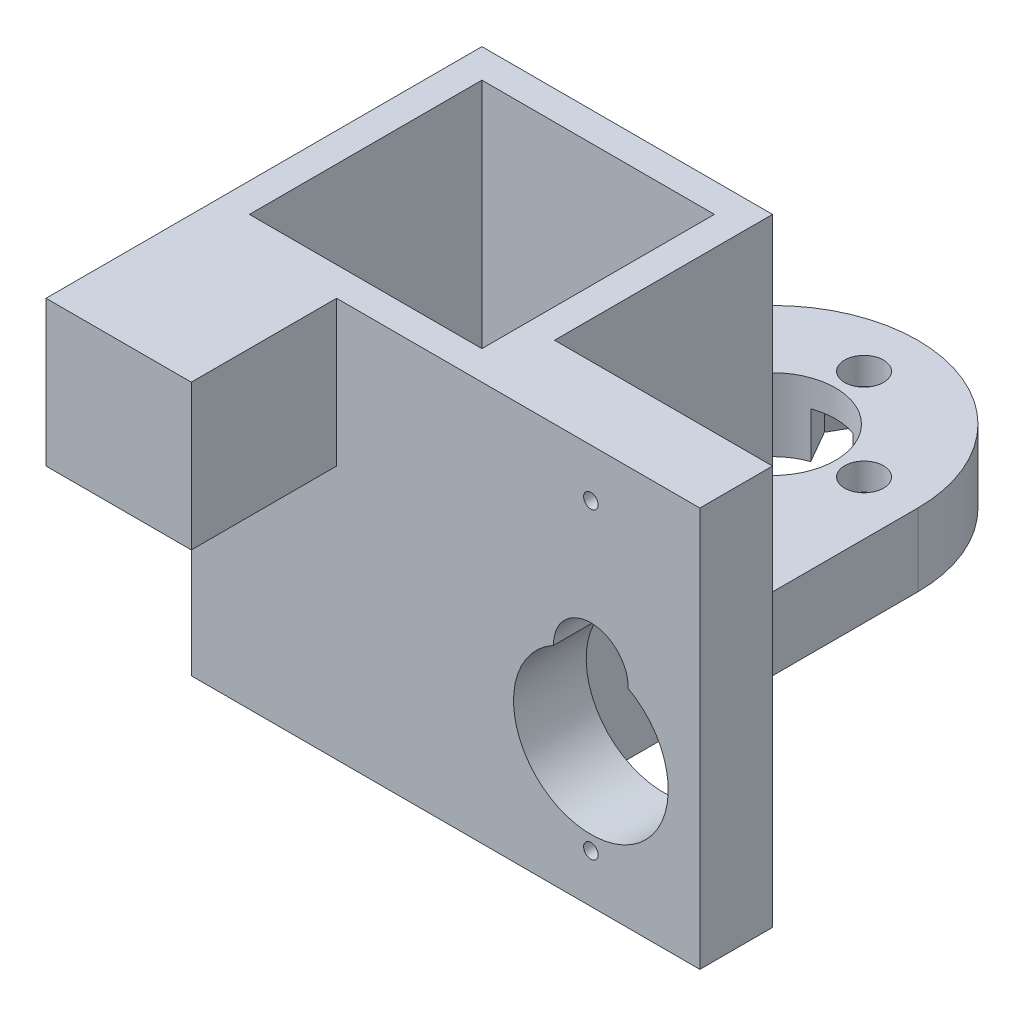
SolidWorks part; units mm, degrees
ref_plane "Front Plane" through (0, 0, 0) normal (0, 0, 1) x (1, 0, 0)
ref_plane "Top Plane" through (0, 0, 0) normal (0, 1, 0) x (1, 0, 0)
ref_plane "Right Plane" through (0, 0, 0) normal (1, 0, 0) x (0, 0, -1)
sketch "Sketch1" plane through (0, 0, 0) normal (0, 1, 0) x (1, 0, 0)
  line L1 (-10.16, 10.16) -> (10.16, 10.16)
  line L2 (-10.16, 10.16) -> (-10.16, -10.16)
  line L3 (-10.16, -10.16) -> (10.16, -10.16)
  line L4 (10.16, 10.16) -> (10.16, -10.16)
  line L5 (-10.16, 10.16) -> (10.16, -10.16) construction
  line L6 (-10.16, -10.16) -> (10.16, 10.16) construction
  line L7 (-12.7, 12.7) -> (12.7, 12.7)
  line L8 (-12.7, 12.7) -> (-12.7, -12.7)
  line L9 (-12.7, -12.7) -> (12.7, -12.7)
  line L10 (12.7, 12.7) -> (12.7, -12.7)
  line L11 (-12.7, 12.7) -> (12.7, -12.7) construction
  line L12 (-12.7, -12.7) -> (12.7, 12.7) construction
  point P0 (0, 0)
  point P6 (0, 0)
  dimension "D1" = 25.4
  dimension "D2" = 20.32
extrude "Boss-Extrude1" add sketch "Sketch1" along normal mid plane 34.925
sketch "Sketch4" plane through (0, -17.4625, 0) normal (0, -1, 0) x (1, 0, 0)
  line L1 (-12.7, -12.7) -> (12.7, -12.7)
  line L2 (-12.7, -12.7) -> (-12.7, -38.1)
  line L3 (-12.7, -38.1) -> (12.7, -38.1)
  line L4 (12.7, -12.7) -> (12.7, -38.1)
  point P5 (0, 0)
extrude "Boss-Extrude2" add sketch "Sketch4" against normal blind 6.35
sketch "Sketch6" plane through (0, -11.1125, 0) normal (0, 1, 0) x (1, 0, 0)
  line L0 (12.7, 38.1) -> (12.7, 12.7) construction
  circle A0 centre (0, 25.4) radius 5.5
  point P2 (0, 0)
  point P6 (12.7, 25.4)
  dimension "D1" = 11
extrude "Cut-Extrude1" cut sketch "Sketch6" against normal up to next
fillet "Fillet1" radius 12.7 2 edges at (-12.7, -14.2875, -38.1) (12.7, -14.2875, -38.1)
hole_wizard "M3 Clearance Hole1" positions "Sketch8" profile "Sketch10" hole size "M3" standard "ANSI Metric" end condition through all
sketch "Sketch8" plane through (0, -11.1125, 0) normal (0, 1, 0) x (1, 0, 0)
  circle A0 centre (0, 25.4) radius 5.5 construction
  point P0 (0, 33.4)
  point P4 (0, 0)
  dimension "D1" = 8
sketch "Sketch10" plane through (0, -11.1125, -33.4) normal (1, 0, 0) x (0, 0, 1)
  line L0 (0, 0) -> (0, 6.35)
  line L1 (0, 6.35) -> (1.7, 6.35)
  line L2 (1.7, 6.35) -> (1.7, 0)
  line L5 (1.7, 0) -> (0, 0)
  line L11 (0, -6.35) -> (0, 107.95) construction
  dimension "Thru Hole Dia." = 3.4
  dimension "Thru Hole Depth" = 6.35
pattern_circular "CirPattern1" count 4 over 360 about axis through (0, -11.1125, -25.4) along (0, 1, 0) of "M3 Clearance Hole1"
sketch "Sketch11" plane through (0, -17.4625, 0) normal (0, -1, 0) x (1, 0, 0)
  line L1 (1.7321, -14.4) -> (-1.7321, -14.4)
  line L2 (-1.7321, -14.4) -> (-3.4641, -17.4)
  line L3 (-3.4641, -17.4) -> (-1.7321, -20.4)
  line L4 (-1.7321, -20.4) -> (1.7321, -20.4)
  line L5 (1.7321, -20.4) -> (3.4641, -17.4)
  line L6 (3.4641, -17.4) -> (1.7321, -14.4)
  circle A0 centre (0, -17.4) radius 3 construction
  point P1 (2.9283, -18.6281)
  point P10 (0, -20.5754)
  dimension "D1" = 6
extrude "Cut-Extrude2" cut sketch "Sketch11" against normal blind 4
pattern_circular "CirPattern2" count 4 over 360 about axis through (0, -17.4635, -25.4) along (0, 1, 0) of "Cut-Extrude2" reverse direction yes
sketch "Sketch12" plane through (0, 0, 12.7) normal (0, 0, 1) x (1, 0, 0)
  line L0 (-12.7, -17.4625) -> (12.7, -17.4625) construction
  line L1 (12.7, 17.4625) -> (31.75, 17.4625)
  line L2 (12.7, 17.4625) -> (12.7, -17.4625)
  line L3 (12.7, -17.4625) -> (31.75, -17.4625)
  line L4 (31.75, 17.4625) -> (31.75, -17.4625)
  dimension "D1" = 19.05
extrude "Boss-Extrude3" add sketch "Sketch12" against normal blind 6.35
ref_plane "Plane2" through (9.525, 0, 0) normal (-1, 0, 0) x (0, 0, 1)
sketch "Sketch13" plane through (-12.7, 0, 0) normal (-1, 0, 0) x (0, 0, 1)
  line L1 (12.7, 17.4625) -> (25.4, 17.4625)
  line L2 (12.7, 17.4625) -> (12.7, 4.7625)
  line L3 (12.7, 4.7625) -> (25.4, 4.7625)
  line L4 (25.4, 17.4625) -> (25.4, 4.7625)
  dimension "D1" = 12.7
  dimension "D2" = 12.7
extrude "Boss-Extrude4" add sketch "Sketch13" against normal blind 12.7
sketch "Sketch15" plane through (0, 0, 6.35) normal (0, 0, -1) x (-1, 0, 0)
  circle A0 centre (-22.225, 13.25) radius 0.635
  arc A1 (-22.8083, 14.0622) -> (-21.6417, 14.0622) centre (-22.225, 13.25) ccw construction
  circle A2 centre (-22.225, -13.25) radius 0.635
  arc A3 (-21.6417, -14.0622) -> (-22.8083, -14.0622) centre (-22.225, -13.25) ccw construction
  dimension "D1" = 1.27
extrude "Cut-Extrude3" cut sketch "Sketch15" against normal up to next
sketch "Sketch16" plane through (0, 0, 12.7) normal (0, 0, 1) x (1, 0, 0)
  arc A0 (19.7799, 0.2292) -> (24.6701, 0.2292) centre (22.225, -5.25) ccw construction
  arc A1 (24.6701, 0.2292) -> (19.7799, 0.2292) centre (22.225, 0.75) ccw construction
  arc A2 (19.7799, 0.2292) -> (24.6701, 0.2292) centre (22.225, -5.25) ccw construction
  arc A3 (24.6701, 0.2292) -> (19.7799, 0.2292) centre (22.225, 0.75) ccw construction
  arc A4 (18.9639, 0.6737) -> (25.4861, 0.6737) centre (22.225, -5.25) ccw
  arc A5 (25.4861, 0.6737) -> (18.9639, 0.6737) centre (22.225, 0.75) ccw
  dimension "D1" = 0.762
extrude "Cut-Extrude4" cut sketch "Sketch16" against normal up to next
